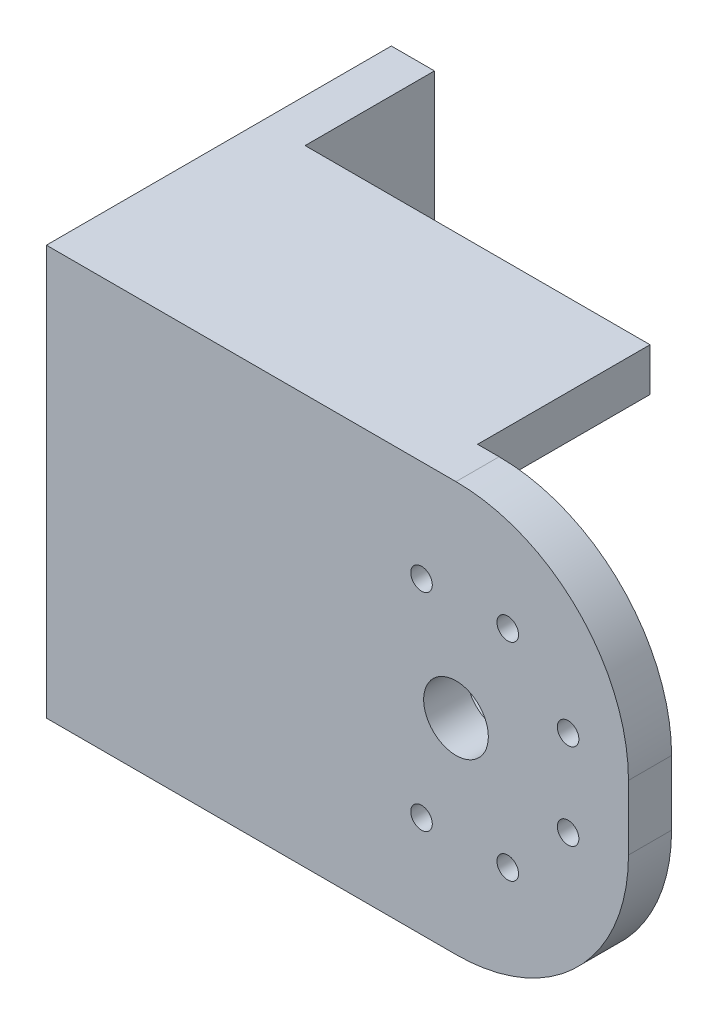
SolidWorks part; units mm, degrees
ref_plane "Front Plane" through (0, 0, 0) normal (0, 0, 1) x (1, 0, 0)
ref_plane "Top Plane" through (0, 0, 0) normal (0, 1, 0) x (1, 0, 0)
ref_plane "Right Plane" through (0, 0, 0) normal (1, 0, 0) x (0, 0, -1)
sketch "Sketch3" plane through (0, 0, 0) normal (0, 0, 1) x (1, 0, 0)
  line L6 (68.6171, 80.0599) -> (163.6171, 80.0599)
  line L10 (68.6171, 80.0599) -> (68.6171, -14.9401)
  line L36 (-101.4371, 49.8561) -> (-17.2351, 49.8561) construction
  line L70 (68.6171, -14.9401) -> (163.6171, -14.9401)
  line L71 (203.6171, 40.0599) -> (203.6171, 25.0599)
  circle A22 centre (163.6171, 32.5599) radius 7.5
  circle A23 centre (189.6171, 42.5599) radius 2.5
  circle A24 centre (155.6171, 56.5599) radius 2.5
  circle A25 centre (175.6171, 56.5599) radius 2.5
  circle A26 centre (155.6171, 8.5599) radius 2.5
  circle A27 centre (175.6171, 8.5599) radius 2.5
  circle A28 centre (189.6171, 22.5599) radius 2.5
  arc A29 (163.6171, -14.9401) -> (203.6171, 25.0599) centre (163.6171, 25.0599) ccw
  arc A30 (163.6171, 80.0599) -> (203.6171, 40.0599) centre (163.6171, 40.0599) cw
  point P23 (203.6171, 80.0599)
  dimension "D2" = 5
  dimension "D3" = 10
  dimension "D4" = 26
  dimension "D7" = 5
  dimension "D21" = 135
  dimension "D22" = 40
  dimension "D23" = 47.5
  dimension "D1" = 15
  dimension "D5" = 5
  dimension "D6" = 5
  dimension "D8" = 5
  dimension "D9" = 5
  dimension "D24" = 40
  dimension "D10" = 8
  dimension "D11" = 24
  dimension "D12" = 20
  dimension "D15" = 20
  dimension "D16" = 8
  dimension "D17" = 20
  dimension "D18" = 48
  dimension "D19" = 48
  dimension "D20" = 95
  dimension "D13" = 26
  dimension "D14" = 24
extrude "Boss-Extrude1" add sketch "Sketch3" along normal blind 10
sketch "Sketch4" plane through (0, 0, 0) normal (0, 0, -1) x (-1, 0, 0)
  line L0 (-68.6171, -14.9401) -> (-163.6171, -14.9401) construction
  line L1 (-68.6171, 80.0599) -> (-78.6171, 80.0599)
  line L2 (-68.6171, 80.0599) -> (-68.6171, -14.9401)
  line L3 (-68.6171, -14.9401) -> (-78.6171, -14.9401)
  line L4 (-78.6171, 80.0599) -> (-78.6171, -14.9401)
  dimension "D1" = 10
extrude "Boss-Extrude2" add sketch "Sketch4" along normal blind 70
sketch "Sketch5" plane through (0, 0, 0) normal (0, 0, -1) x (-1, 0, 0)
  line L1 (-78.6171, 80.0599) -> (-158.6171, 80.0599)
  line L2 (-78.6171, 80.0599) -> (-78.6171, 70.0599)
  line L3 (-78.6171, 70.0599) -> (-158.6171, 70.0599)
  line L4 (-158.6171, 80.0599) -> (-158.6171, 70.0599)
  line L5 (-78.6171, -14.9401) -> (-158.6171, -14.9401)
  line L6 (-78.6171, -14.9401) -> (-78.6171, -4.9401)
  line L7 (-78.6171, -4.9401) -> (-158.6171, -4.9401)
  line L8 (-158.6171, -14.9401) -> (-158.6171, -4.9401)
  dimension "D1" = 10
  dimension "D2" = 10
  dimension "D3" = 80
  dimension "D4" = 80
extrude "Boss-Extrude3" add sketch "Sketch5" along normal blind 40
sketch "Sketch6" plane through (0, -14.9401, 0) normal (0, -1, 0) x (1, 0, 0)
  line L0 (52.25, 0) -> (-52.25, 0) construction
  line L1 (88.6171, 0) -> (120.6171, 0)
  line L2 (88.6171, 0) -> (88.6171, -36)
  line L3 (88.6171, -36) -> (120.6171, -36)
  line L4 (120.6171, 0) -> (120.6171, -36)
  line L5 (68.6171, 10) -> (68.6171, -70) construction
  dimension "D1" = 20
  dimension "D2" = 36
  dimension "D3" = 32
extrude "Cut-Extrude1" cut sketch "Sketch6" against normal blind 43.8
fillet "Fillet2" [suppressed] radius 15
sketch "Sketch8" plane through (68.6171, 0, 0) normal (-1, 0, 0) x (0, 0, 1)
  line L0 (10, 80.0599) -> (-70, 80.0599) construction
  line L1 (-40, 32.5599) -> (-56.1679, 25.863) construction
  line L2 (-70, 32.5599) -> (0, 32.5599) construction
  line L3 (-70, -14.9401) -> (-70, 80.0599) construction
  circle A0 centre (-40, 32.5599) radius 7.5
  circle A1 centre (-56.1679, 25.863) radius 2.5
  circle A2 centre (-56.1679, 39.2569) radius 2.5
  circle A3 centre (-46.697, 48.7278) radius 2.5
  circle A4 centre (-33.303, 48.7278) radius 2.5
  circle A5 centre (-23.8321, 39.2569) radius 2.5
  circle A6 centre (-23.8321, 25.863) radius 2.5
  circle A7 centre (-33.303, 16.392) radius 2.5
  circle A8 centre (-46.697, 16.392) radius 2.5
  point P27 (-40, 32.5599)
  dimension "D1" = 15
  dimension "D6" = 5
  dimension "D2" = 47.5
  dimension "D3" = 30
  dimension "D4" = 17.5
  dimension "D5" = 22.5
  dimension "D7" = 8
extrude "Cut-Extrude2" cut sketch "Sketch8" against normal blind 43.8
